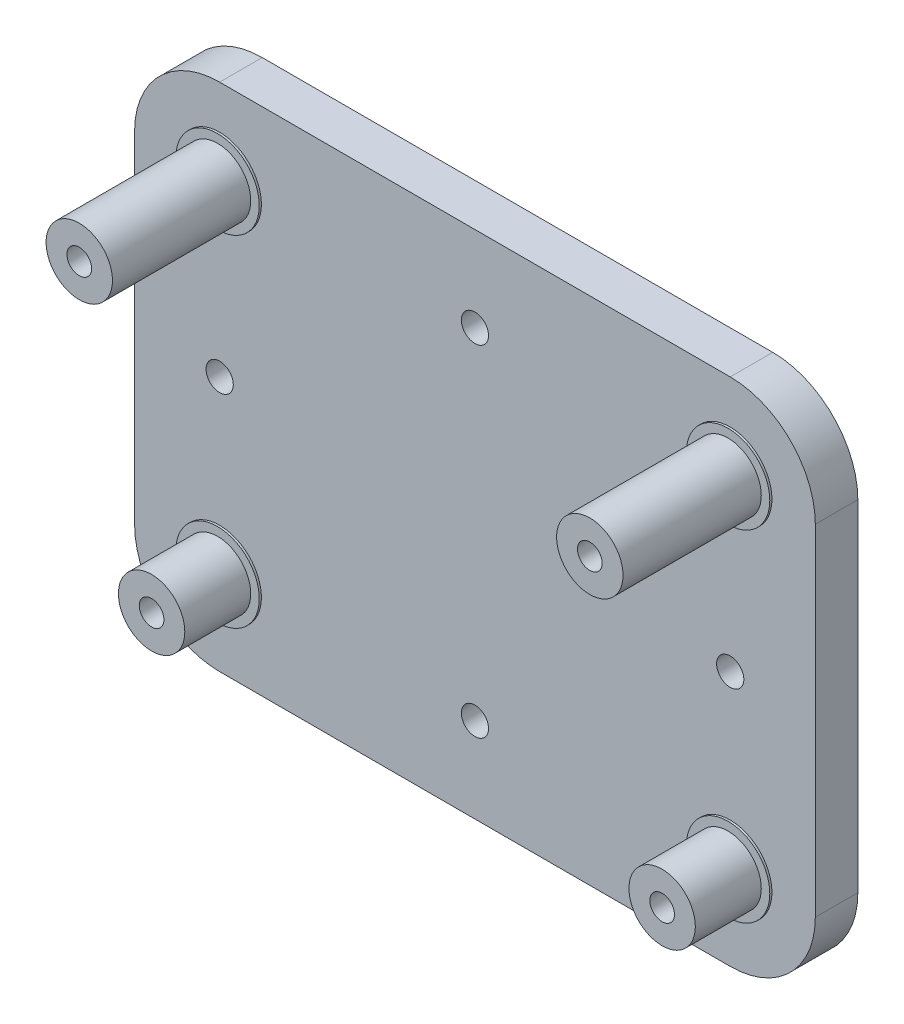
SolidWorks part; units mm, degrees
ref_plane "Front Plane" through (0, 0, 0) normal (0, 0, 1) x (1, 0, 0)
ref_plane "Top Plane" through (0, 0, 0) normal (0, 1, 0) x (1, 0, 0)
ref_plane "Right Plane" through (0, 0, 0) normal (1, 0, 0) x (0, 0, -1)
ref_axis "X" through (-88.99, 0, 0) along (1, 0, 0)
ref_axis "Y" through (0, 55, 0) along (0, -1, 0)
ref_axis "Z" through (0, 0, -88.99) along (0, 0, 1)
sketch "Sketch1" plane through (0, 0, 0) normal (0, 0, 1) x (1, 0, 0)
  line L1 (-30, 20) -> (30, 20) construction
  line L2 (-30, 20) -> (-30, -20) construction
  line L3 (-30, -20) -> (30, -20) construction
  line L4 (30, 20) -> (30, -20) construction
  line L5 (-30, 20) -> (30, -20) construction
  line L6 (-30, -20) -> (30, 20) construction
  line L7 (-40, 30) -> (40, 30)
  line L8 (-40, 30) -> (-40, -30)
  line L9 (-40, -30) -> (40, -30)
  line L10 (40, 30) -> (40, -30)
  line L11 (-40, 30) -> (40, -30) construction
  line L12 (-40, -30) -> (40, 30) construction
  circle A0 centre (-30, 20) radius 3.9
  circle A1 centre (-30, -20) radius 3.9
  circle A2 centre (30, -20) radius 3.9
  circle A3 centre (30, 20) radius 3.9
  circle A4 centre (-30, 20) radius 4.9
  circle A5 centre (30, 20) radius 4.9
  circle A6 centre (30, -20) radius 4.9
  circle A7 centre (-30, -20) radius 4.9
  circle A8 centre (-30, 20) radius 1.45
  circle A9 centre (-30, -20) radius 1.45
  circle A10 centre (30, 20) radius 1.45
  circle A11 centre (30, -20) radius 1.45
  circle A12 centre (-30, 0) radius 1.6
  circle A13 centre (0, 20) radius 1.6
  circle A14 centre (30, 0) radius 1.6
  circle A15 centre (0, -20) radius 1.6
  point P0 (0, 0)
  point P10 (0, 0)
  dimension "D1" = 40
  dimension "D3" = 7.8
  dimension "D6" = 1
  dimension "D7" = 2.9
  dimension "D8" = 3.2
  dimension "D2" = 60
  dimension "D4" = 10
  dimension "D5" = 10
extrude "Boss-Extrude1" add sketch "Sketch1" against normal blind 5 contours L8 L9 L10 L7
extrude "Boss-Extrude2" add sketch "Sketch1<3>" along normal blind 8 contours A1 A9 | A2 A11 region at (-33.7897, -20, 0) region at (26.2103, -20, 0)
sketch "Sketch1<3>" plane through (0, 0, 0) normal (0, 0, 1) x (1, 0, 0) same geometry as "Sketch1"
extrude "Boss-Extrude4" add sketch "Sketch1<5>" along normal blind 16.5 contours A0 A8 | A3 A10 region at (-33.7897, 20, 0) region at (26.2103, 20, 0)
sketch "Sketch1<5>" plane through (0, 0, 0) normal (0, 0, 1) x (1, 0, 0) same geometry as "Sketch1"
extrude "Boss-Extrude3" add sketch "Sketch1<4>" along normal blind 0.25 contours A4 A0 | A5 A3 | A6 A2 | A7 A1 region at (-34.7614, 20, 0) region at (25.2386, 20, 0) region at (25.2386, -20, 0) region at (-34.7614, -20, 0)
sketch "Sketch1<4>" plane through (0, 0, 0) normal (0, 0, 1) x (1, 0, 0) same geometry as "Sketch1"
extrude "Cut-Extrude1" cut sketch "Sketch1<6>" against normal through all both and the other way through all contours A13 | A12 | A15 | A14 region at (-30, 0, 0) region at (0, 20, 0) region at (30, 0, 0) region at (0, -20, 0)
sketch "Sketch1<6>" plane through (0, 0, 0) normal (0, 0, 1) x (1, 0, 0) same geometry as "Sketch1"
fillet "Fillet1" radius 10 4 edges at (40, 30, -2.5) (40, -30, -2.5) (-40, -30, -2.5) (-40, 30, -2.5)
